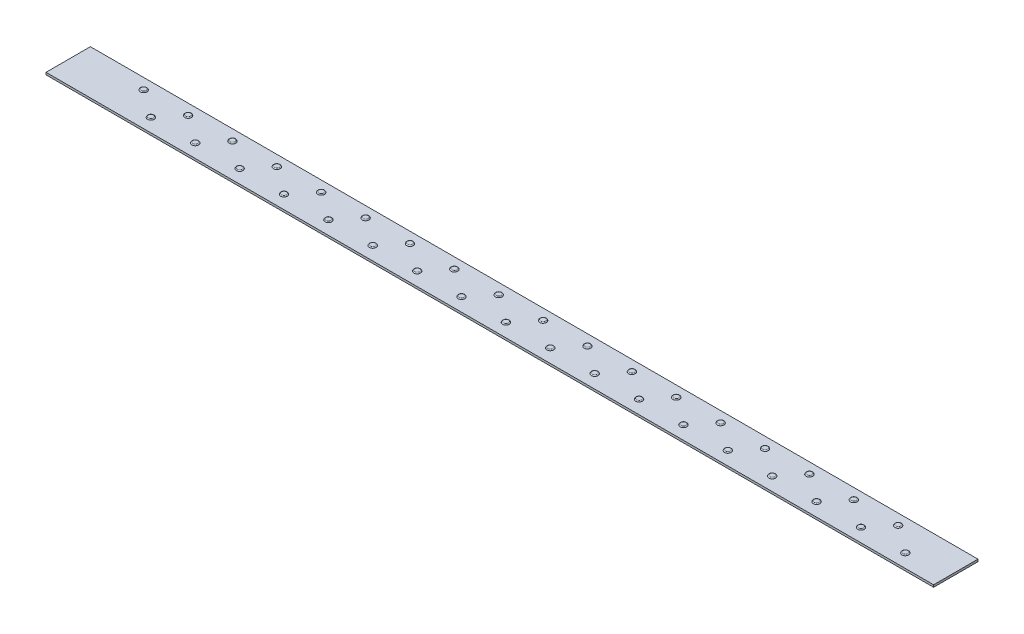
SolidWorks part; units mm, degrees
ref_plane "Alzado" through (0, 0, 0) normal (0, 0, 1) x (1, 0, 0)
ref_plane "Planta" through (0, 0, 0) normal (0, 1, 0) x (1, 0, 0)
ref_plane "Vista lateral" through (0, 0, 0) normal (1, 0, 0) x (0, 0, -1)
sketch "Croquis1" plane through (0, 0, 0) normal (0, 1, 0) x (1, 0, 0)
  line L1 (-20000, 1000) -> (20000, 1000)
  line L2 (-20000, 1000) -> (-20000, -1000)
  line L3 (-20000, -1000) -> (20000, -1000)
  line L4 (20000, 1000) -> (20000, -1000)
  line L5 (-20000, 1000) -> (20000, -1000) construction
  line L6 (-20000, -1000) -> (20000, 1000) construction
  point P0 (0, 0)
  dimension "D1" = 40000
  dimension "D2" = 2000
extrude "Saliente-Extruir1" add sketch "Croquis1" along normal blind 100
sketch "Croquis2" plane through (0, 100, 0) normal (0, 1, 0) x (1, 0, 0)
  circle A3 centre (-17108.0521, 509.9314) radius 150
  circle A4 centre (-15874.2708, -400) radius 150
  circle A5 centre (-13874.2708, -400) radius 150
  circle A6 centre (-15108.0521, 509.9314) radius 150
  circle A7 centre (-11874.2708, -400) radius 150
  circle A8 centre (-13108.0521, 509.9314) radius 150
  circle A9 centre (-9874.2708, -400) radius 150
  circle A10 centre (-11108.0521, 509.9314) radius 150
  circle A11 centre (-7874.2708, -400) radius 150
  circle A12 centre (-9108.0521, 509.9314) radius 150
  circle A13 centre (-5874.2708, -400) radius 150
  circle A14 centre (-7108.0521, 509.9314) radius 150
  circle A15 centre (-3874.2708, -400) radius 150
  circle A16 centre (-5108.0521, 509.9314) radius 150
  circle A17 centre (-1874.2708, -400) radius 150
  circle A18 centre (-3108.0521, 509.9314) radius 150
  circle A19 centre (125.7292, -400) radius 150
  circle A20 centre (-1108.0521, 509.9314) radius 150
  circle A21 centre (2125.7292, -400) radius 150
  circle A22 centre (891.9479, 509.9314) radius 150
  circle A23 centre (4125.7292, -400) radius 150
  circle A24 centre (2891.9479, 509.9314) radius 150
  circle A25 centre (6125.7292, -400) radius 150
  circle A26 centre (4891.9479, 509.9314) radius 150
  circle A27 centre (8125.7292, -400) radius 150
  circle A28 centre (6891.9479, 509.9314) radius 150
  circle A29 centre (10125.7292, -400) radius 150
  circle A30 centre (8891.9479, 509.9314) radius 150
  circle A31 centre (12125.7292, -400) radius 150
  circle A32 centre (10891.9479, 509.9314) radius 150
  circle A33 centre (14125.7292, -400) radius 150
  circle A34 centre (12891.9479, 509.9314) radius 150
  circle A35 centre (16125.7292, -400) radius 150
  circle A36 centre (14891.9479, 509.9314) radius 150
  circle A37 centre (18125.7292, -400) radius 150
  circle A38 centre (16891.9479, 509.9314) radius 150
  dimension "D1" = 18
extrude "Saliente-Extruir2" add sketch "Croquis2" along normal blind 40
fillet "Redondeo1" radius 40 36 edges at (18125.7292, 140, 550) (16891.9479, 140, -359.9314) (16125.7292, 140, 550) (14891.9479, 140, -359.9314) (14125.7292, 140, 550) (12891.9479, 140, -359.9314) (12125.7292, 140, 550) (10891.9479, 140, -359.9314) (10125.7292, 140, 550) (8891.9479, 140, -359.9314) (8125.7292, 140, 550) (6891.9479, 140, -359.9314) (6125.7292, 140, 550) (4891.9479, 140, -359.9314) (4125.7292, 140, 550) (2891.9479, 140, -359.9314) (2125.7292, 140, 550) (891.9479, 140, -359.9314) (125.7292, 140, 550) (-1108.0521, 140, -359.9314) (-1874.2708, 140, 550) (-3108.0521, 140, -359.9314) (-3874.2708, 140, 550) (-5108.0521, 140, -359.9314) (-5874.2708, 140, 550) (-7108.0521, 140, -359.9314) (-7874.2708, 140, 550) (-9108.0521, 140, -359.9314) (-9874.2708, 140, 550) (-11108.0521, 140, -359.9314) (-11874.2708, 140, 550) (-13108.0521, 140, -359.9314) (-13874.2708, 140, 550) (-15108.0521, 140, -359.9314) (-15874.2708, 140, 550) (-17108.0521, 140, -359.9314)
